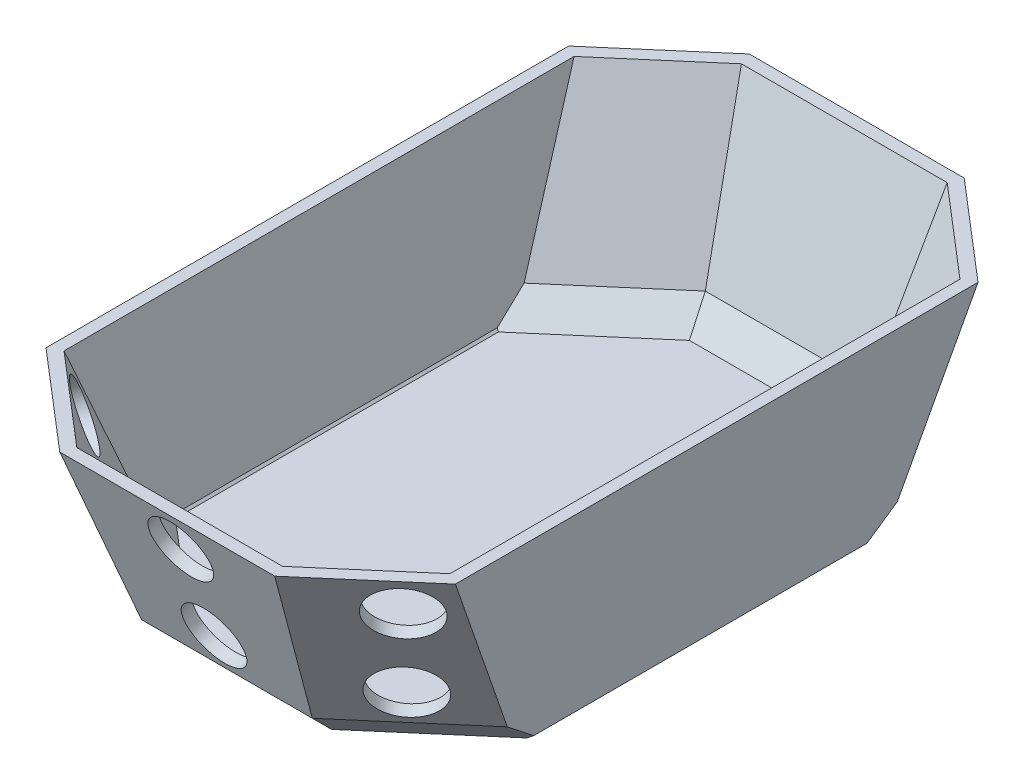
SolidWorks part; units mm, degrees
note: '?' marks a value the reader was unsure of.
material "Balsa"
ref_plane "Front Plane" through (0, 0, 0) normal (0, 0, 1) x (1, 0, 0)
ref_plane "Top Plane" through (0, 0, 0) normal (0, 1, 0) x (1, 0, 0)
ref_plane "Right Plane" through (0, 0, 0) normal (1, 0, 0) x (0, 0, -1)
ref_axis "X" through (-88.99, 0, 0) along (1, 0, 0)?
ref_axis "Y" through (0, 55, 0) along (0, -1, 0)?
ref_axis "Z" through (0, 0, -88.99) along (0, 0, 1)?
sketch "Sketch1" plane through (0, 0, 0) normal (0, 1, 0) x (1, 0, 0)
  line L0 (-48.2247, 46.933) -> (-20.883, 70.3995)
  line L1 (-48.2247, 46.933) -> (48.2247, 46.933)
  line L2 (-48.2247, 46.933) -> (-48.2247, -46.933)
  line L3 (-48.2247, -46.933) -> (48.2247, -46.933)
  line L4 (48.2247, 46.933) -> (48.2247, -46.933)
  line L5 (-48.2247, 46.933) -> (48.2247, -46.933) construction
  line L6 (-48.2247, -46.933) -> (48.2247, 46.933) construction
  line L7 (-20.883, 70.3995) -> (20.883, 70.3995)
  line L8 (20.883, 70.3995) -> (48.2247, 46.933)
  line L9 (0, 70.3995) -> (0, 46.933) construction
  line L10 (-48.2247, 0) -> (0, 0) construction
  line L11 (20.883, -70.3995) -> (48.2247, -46.933)
  line L12 (-20.883, -70.3995) -> (20.883, -70.3995)
  line L13 (-48.2247, -46.933) -> (-20.883, -70.3995)
  point P0 (0, 0)
extrude "Boss-Extrude1" add sketch "Sketch1" along normal blind 50 contours L4 L1 L2 L3 | L8 L7 L0 L1 | L3 L13 L12 L11
draft "Draft1" type of draft neutral plane draft angle 20 faces to draft 6 face at (-34.5539, 25, 58.6663) face at (-34.5539, 25, -58.6663) face at (0, 25, -70.3995) face at (34.5539, 25, -58.6663) face at (34.5539, 25, 58.6663) face at (0, 25, 70.3995) neutral plane through (0, 0, 0) neutral plane normal (0, -1, 0) parameters "D1"=20
draft "Draft2" type of draft neutral plane draft angle 5 faces to draft 2 face at (48.2247, 25, 0) face at (-48.2247, 25, 0) neutral plane through (0, 0, 0) neutral plane normal (0, -1, 0) parameters "D1"=5
chamfer "Chamfer1" distance 5 angle 45 6 edges at (34.5539, 0, -58.6663) (0, 0, -70.3995) (-34.5539, 0, -58.6663) (-34.5539, 0, 58.6663) (0, 0, 70.3995) (34.5539, 0, 58.6663)
chamfer "Chamfer2" distance 2 angle 45 2 edges at (-48.2247, 0, 0) (48.2247, 0, 0)
shell "Shell1" thickness 3
sketch "Sketch2" plane through (36.7084, -20.5145, 42.7703) normal (-0.612, 0.342, -0.7131) x (-0.7909, -0.2647, 0.5518)
  line L0 (1.504, 43.1234) -> (-5.5375, 67.1112) construction
  line L1 (19.8842, 39.139) -> (-11.8064, 29.8364) construction
  line L2 (19.8842, 39.139) -> (-11.8064, 29.8364)
  line L3 (1.504, 43.1234) -> (4.0389, 34.4877) construction
  circle A0 centre (-5.5375, 67.1112) radius 8
  circle A1 centre (1.504, 43.1234) radius 8
  dimension "D3" = 16
  dimension "D1" = 25
  dimension "D2" = 9
extrude "Cut-Extrude1" cut sketch "Sketch2" against normal through all contours A0 | A1
sketch "Sketch3" plane through (0, -21.5999, 59.3453) normal (0, 0.342, -0.9397) x (-1, 0, 0)
  line L0 (20.9829, 33.1089) -> (-20.9829, 33.1089) construction
  line L1 (20.9829, 33.1089) -> (-20.9829, 33.1089)
  line L2 (0, 33.1089) -> (0, 42.1089) construction
  line L3 (0, 42.1089) -> (0, 67.1089) construction
  circle A0 centre (0, 67.1089) radius 8
  circle A1 centre (0, 42.1089) radius 8
  dimension "D1" = 25
  dimension "D2" = 16
  dimension "D3" = 9
extrude "Cut-Extrude2" cut sketch "Sketch3" against normal through all contours A0 | A1
mirror "Mirror1" about plane through (0, 0, 0) normal (1, 0, 0) of "Cut-Extrude1"
